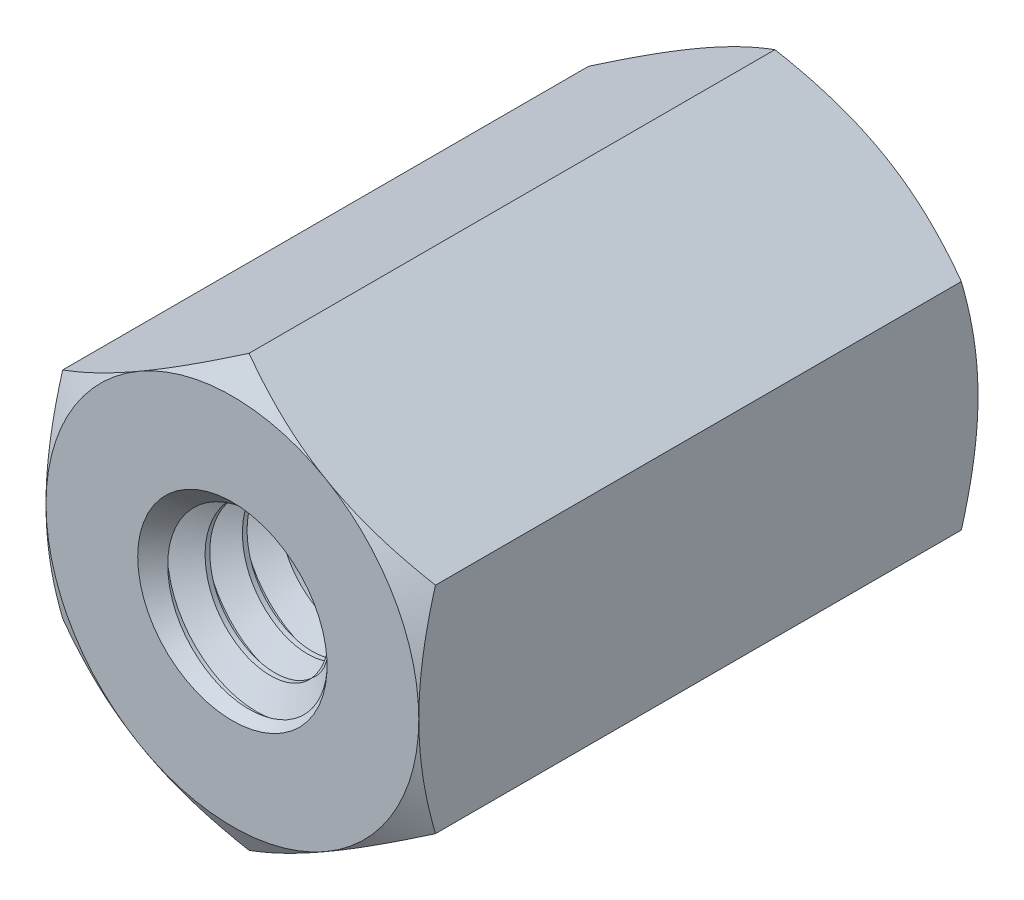
SolidWorks part; units mm, degrees
ref_plane "Front Plane" through (0, 0, 0) normal (0, 0, 1) x (1, 0, 0)
ref_plane "Top Plane" through (0, 0, 0) normal (0, 1, 0) x (1, 0, 0)
ref_plane "Right Plane" through (0, 0, 0) normal (1, 0, 0) x (0, 0, -1)
sketch "Sketch3" plane through (0, 0, 0) normal (1, 0, 0) x (0, 0, -1)
  line L0 (-9.525, 0) -> (9.525, 0) construction
  line L1 (0, 6.35) -> (0, -6.35) construction
  line L2 (-9.525, 3.175) -> (-9.525, -3.175) construction
  point P2 (-6.35, 0)
  point P3 (6.35, 0)
  dimension "Length" = 19.05
  dimension "Min Thread Length" = 15.875
  dimension "D1" = 15.875
  dimension "Thread Dia" = 6.35
  dimension "Hex" = 12.7
sketch "Sketch1" plane through (0, 0, 0) normal (0, 0, 1) x (1, 0, 0)
  line L1 (0, 7.3323) -> (-6.35, 3.6662)
  line L2 (-6.35, 3.6662) -> (-6.35, -3.6662)
  line L3 (-6.35, -3.6662) -> (0, -7.3323)
  line L4 (0, -7.3323) -> (6.35, -3.6662)
  line L5 (6.35, -3.6662) -> (6.35, 3.6662)
  line L6 (6.35, 3.6662) -> (0, 7.3323)
  circle A0 centre (0, 0) radius 6.35 construction
  circle A1 centre (0, 0) radius 3.175
extrude "Extrude1" add sketch "Sketch1" along normal up to vertex (9.525 mm away) and the other way up to vertex (9.525 mm away) up to point (0, 0, 9.525) other way up to point (0, 0, -9.525)
sketch "Sketch11" plane through (0, 0, -9.525) normal (0, 0, -1) x (-1, 0, 0)
  circle A0 centre (0, 0) radius 3.175 construction
  circle A1 centre (0, 0) radius 3.175
curve "Helix/Spiral1" pitch 1.27 height 20.32 radius 3.175 centre (0, 0, -9.525) axis (0, 0, 1) start towards (0, 1, 0) parameters "Pitch"=1.27
sketch "Sketch12" plane through (0, 0, 0) normal (1, 0, 0) x (0, 0, -1)
  line L0 (10.6362, 3.175) -> (9.525, 3.175)
  line L1 (10.6362, 3.175) -> (10.16, 2.3501)
  line L2 (10.16, 2.3501) -> (10.0012, 2.3501)
  line L3 (10.0012, 2.3501) -> (9.525, 3.175)
  line L4 (10.0806, 2.3501) -> (10.0806, 3.175) construction
  line L5 (10.3981, 2.7626) -> (9.7631, 2.7626) construction
  dimension "D1" = 0.1588
  dimension "D2" = 0.635
  dimension "D3" = 60
sweep "Sweep1" add profiles "Sketch12" path "Helix/Spiral1"
sketch "Sketch6" plane through (0, 0, -9.525) normal (0, 0, -1) x (-1, 0, 0)
  line L6 (0, 7.3323) -> (-6.35, 3.6662)
  line L7 (-6.35, 3.6662) -> (-6.35, -3.6662)
  line L8 (-6.35, -3.6662) -> (0, -7.3323)
  line L9 (0, -7.3323) -> (6.35, -3.6662)
  line L10 (6.35, -3.6662) -> (6.35, 3.6662)
  line L11 (6.35, 3.6662) -> (0, 7.3323)
  line L12 (0, 7.3323) -> (-6.35, 3.6662)
  line L13 (-6.35, 3.6662) -> (-6.35, -3.6662)
  line L14 (-6.35, -3.6662) -> (0, -7.3323)
  line L15 (0, -7.3323) -> (6.35, -3.6662)
  line L16 (6.35, -3.6662) -> (6.35, 3.6662)
  line L17 (6.35, 3.6662) -> (0, 7.3323)
  dimension "D1" = 0
extrude "Extrude2" cut sketch "Sketch6" along normal through all
sketch "Sketch7" plane through (0, 0, -9.525) normal (0, 0, -1) x (-1, 0, 0)
  circle A2 centre (0, 0) radius 3.2258
  circle A3 centre (0, 0) radius 3.2258
  dimension "D1" = 0.0508
extrude "Extrude3" cut sketch "Sketch7" against normal through all draft 43
sketch "Sketch8" plane through (0, 0, -9.525) normal (0, 0, -1) x (-1, 0, 0)
  circle A0 centre (0, 0) radius 6.35 construction
  circle A1 centre (0, 0) radius 6.35
extrude "Extrude4" cut sketch "Sketch8" against normal through all draft 60 flip side to cut
mirror "Mirror1" about plane through (0, 0, 0) normal (0, 0, 1) of "Extrude2", "Extrude3", "Extrude4"
sketch "Sketch9" [suppressed] plane through (0, 0, 0) normal (1, 0, 0) x (0, 0, -1)
  line L1 (-22.225, 3.2258) -> (22.225, 3.2258)
  line L2 (-22.225, 3.2258) -> (-22.225, 0)
  line L3 (-22.225, 0) -> (22.225, 0)
  line L4 (22.225, 3.2258) -> (22.225, 0)
  line L7 (-38.1, 0) -> (38.1, 0) construction
revolve "Revolve" [suppressed] add sketch "Sketch9" angle 360 about L0
sketch "Sketch10" [suppressed] plane through (0, 0, 0) normal (1, 0, 0) x (0, 0, -1)
  line L0 (38.1, 3.175) -> (22.225, 3.175)
  line L1 (-38.1, 3.175) -> (-22.225, 3.175)
  line L2 (22.225, 3.175) -> (22.225, -3.175)
  line L3 (-38.1, -3.2258) -> (-22.225, -3.2258)
  line L4 (-22.225, 3.175) -> (-22.225, -3.2258)
  line L5 (22.225, -3.175) -> (38.1, -3.175)
equation "\"D1@Sketch3\" = \"Min Thread Length@Sketch3\""
equation "\"D3@Helix/Spiral1\" = \"Length@Sketch3\"+\"Pitch@Helix/Spiral1\""
equation "\"D1@Sketch12\" = \"Pitch@Helix/Spiral1\"*.125"
equation "\"D2@Sketch12\" = \"Pitch@Helix/Spiral1\"*.5"
